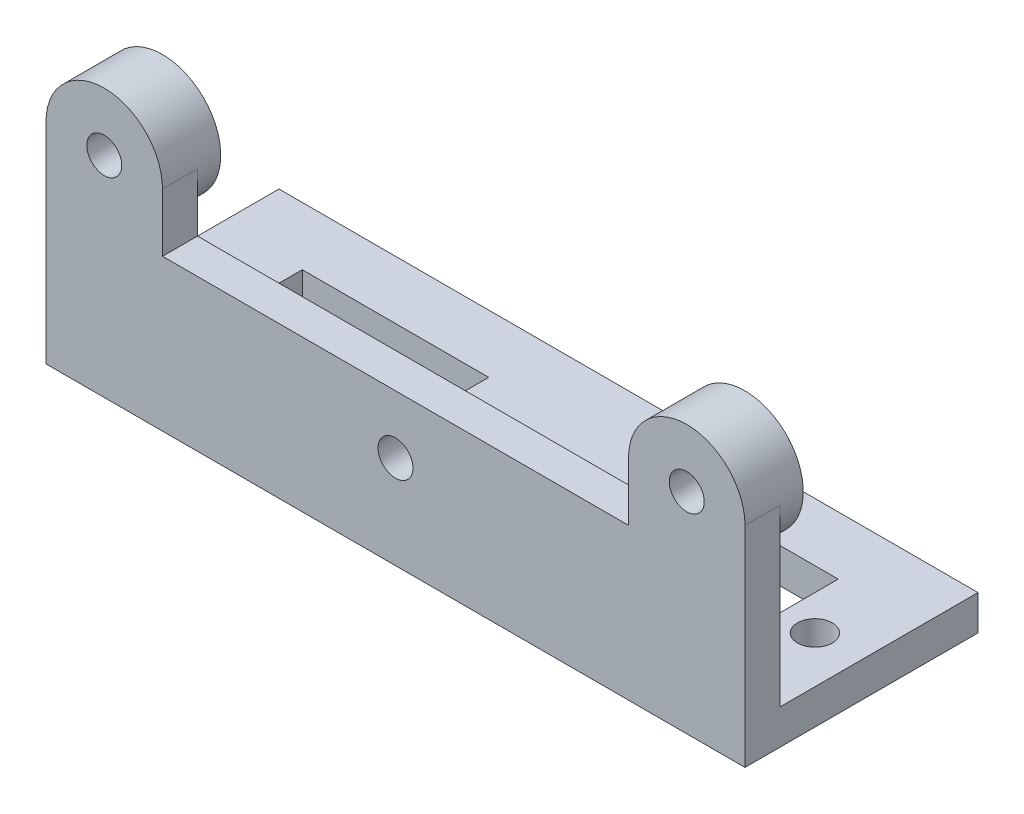
SolidWorks part; units mm, degrees
ref_plane "Front Plane" through (0, 0, 0) normal (0, 0, 1) x (1, 0, 0)
ref_plane "Top Plane" through (0, 0, 0) normal (0, 1, 0) x (1, 0, 0)
ref_plane "Right Plane" through (0, 0, 0) normal (1, 0, 0) x (0, 0, -1)
sketch "Sketch1" plane through (0, 0, 0) normal (0, 1, 0) x (1, 0, 0)
  line L0 (0, 127) -> (-76.2, 127)
  line L1 (0, 0) -> (406.4, 0)
  line L2 (0, 0) -> (0, 254)
  line L3 (0, 254) -> (406.4, 254)
  line L4 (406.4, 0) -> (406.4, 254)
  line L5 (406.4, 127) -> (482.6, 127)
  line L6 (482.6, 127) -> (685.8, 127)
  line L7 (762, 127) -> (685.8, 127)
  line L8 (1168.4, 127) -> (1244.6, 127)
  line L9 (762, 0) -> (1168.4, 0)
  line L10 (762, 0) -> (762, 254)
  line L11 (1168.4, 0) -> (1168.4, 254)
  line L12 (762, 254) -> (1168.4, 254)
  line L13 (-114.3, 127) -> (-177.8, 127)
  line L14 (-177.8, 127) -> (-177.8, 381)
  line L15 (1282.7, 127) -> (1346.2, 127)
  line L16 (1346.2, 127) -> (1346.2, -127)
  line L18 (-177.8, 381) -> (1346.2, 381)
  line L19 (-177.8, 381) -> (-177.8, -127)
  line L20 (-177.8, -127) -> (1346.2, -127)
  line L21 (1346.2, 381) -> (1346.2, -127)
  circle A0 centre (-76.2, 127) radius 38.1
  circle A1 centre (482.6, 127) radius 38.1
  circle A2 centre (1244.6, 127) radius 38.1
  circle A3 centre (685.8, 127) radius 38.1
extrude "Boss-Extrude2" add sketch "Sketch1" along normal blind 76.2 contours A3 L7 L10 L12 L11 L8 A2 L15 L21 L18 L14 L13 A0 L0 L2 L3 L4 L5 A1 L6 | A3 L6 A1 L5 L4 L1 L2 L0 A0 L13 L19 L20 L16 L15 A2 L8 L11 L9 L10 L7
scale "Scale2" scale about centroid uniform scaling yes scale factor 0.03937
sketch "Sketch3" plane through (0, 0, -117) normal (0, 0, 1) x (1, 0, 0)
  line L0 (554.2, 49.6) -> (554.2, 59.6)
  line L1 (554.2, 39.6) -> (614.2, 39.6)
  line L2 (554.2, 39.6) -> (554.2, 49.6)
  line L3 (554.2, 49.6) -> (614.2, 49.6)
  line L4 (614.2, 39.6) -> (614.2, 49.6)
  line L5 (554.2, 59.6) -> (564.2, 59.6)
  line L6 (564.2, 59.6) -> (564.2, 49.6)
  line L7 (584.2, 39.6) -> (584.2, 44.6)
  line L8 (614.2, 49.6) -> (604.2, 49.6)
  line L9 (614.2, 49.6) -> (614.2, 59.6)
  line L10 (614.2, 59.6) -> (604.2, 59.6)
  line L11 (604.2, 49.6) -> (604.2, 59.6)
  line L12 (559.2, 59.6) -> (559.2, 54.6)
  line L13 (609.2, 59.6) -> (609.2, 54.6)
  circle A3 centre (584.2, 44.6) radius 1.5
  circle A4 centre (559.2, 54.6) radius 1.5
  circle A5 centre (609.2, 54.6) radius 1.5
extrude "Boss-Extrude3" add sketch "Sketch3" against normal blind 3
sketch "Sketch4" plane through (0, 0, -120) normal (0, 0, -1) x (-1, 0, 0)
  circle A0 centre (-559.2, 54.6) radius 5
  circle A1 centre (-609.2, 54.6) radius 5
  circle A2 centre (-609.2, 54.6) radius 1.5 construction
  circle A3 centre (-559.2, 54.6) radius 1.5 construction
  circle A4 centre (-609.2, 54.6) radius 1.5
  circle A5 centre (-559.2, 54.6) radius 1.5
extrude "Boss-Extrude5" add sketch "Sketch4" along normal blind 2
sketch "Sketch5" plane through (0, 0, -122) normal (0, 0, -1) x (-1, 0, 0)
  line L0 (-609.2, 59.6) -> (-614.2, 59.6) construction
  line L1 (-614.2, 59.6) -> (-614.2, 54.6) construction
  line L2 (-604.2, 54.6) -> (-604.2, 59.6) construction
  line L3 (-604.2, 59.6) -> (-609.2, 59.6) construction
  line L4 (-559.2, 59.6) -> (-564.2, 59.6) construction
  line L5 (-564.2, 59.6) -> (-564.2, 54.6) construction
  line L6 (-554.2, 54.6) -> (-554.2, 59.6) construction
  line L7 (-554.2, 59.6) -> (-559.2, 59.6) construction
  line L8 (-609.2, 59.6) -> (-614.2, 59.6)
  line L9 (-614.2, 59.6) -> (-614.2, 54.6)
  line L10 (-604.2, 54.6) -> (-604.2, 59.6)
  line L11 (-604.2, 59.6) -> (-609.2, 59.6)
  line L12 (-559.2, 59.6) -> (-564.2, 59.6)
  line L13 (-564.2, 59.6) -> (-564.2, 54.6)
  line L14 (-554.2, 54.6) -> (-554.2, 59.6)
  line L15 (-554.2, 59.6) -> (-559.2, 59.6)
  arc A0 (-609.2, 59.6) -> (-614.2, 54.6) centre (-609.2, 54.6) ccw construction
  arc A1 (-604.2, 54.6) -> (-609.2, 59.6) centre (-609.2, 54.6) ccw construction
  arc A2 (-559.2, 59.6) -> (-564.2, 54.6) centre (-559.2, 54.6) ccw construction
  arc A3 (-554.2, 54.6) -> (-559.2, 59.6) centre (-559.2, 54.6) ccw construction
  arc A4 (-609.2, 59.6) -> (-614.2, 54.6) centre (-609.2, 54.6) ccw
  arc A5 (-604.2, 54.6) -> (-609.2, 59.6) centre (-609.2, 54.6) ccw
  arc A6 (-559.2, 59.6) -> (-564.2, 54.6) centre (-559.2, 54.6) ccw
  arc A7 (-554.2, 54.6) -> (-559.2, 59.6) centre (-559.2, 54.6) ccw
extrude "Cut-Extrude1" cut sketch "Sketch5" against normal blind 29 contours A7 L14 L15 | L12 L13 A6 | A5 L10 L11 | L8 L9 A4
